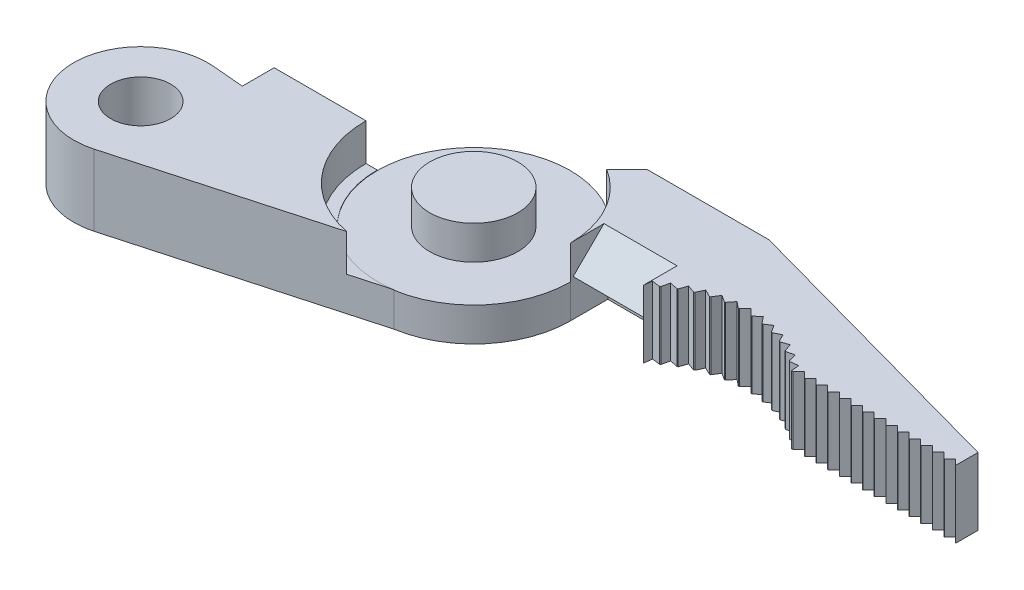
SolidWorks part; units mm, degrees
material "Plain Carbon Steel"
ref_plane "Front Plane" through (0, 0, 0) normal (0, 0, 1) x (1, 0, 0)
ref_plane "Top Plane" through (0, 0, 0) normal (0, 1, 0) x (1, 0, 0)
ref_plane "Right Plane" through (0, 0, 0) normal (1, 0, 0) x (0, 0, -1)
sketch "Sketch1" plane through (0, 0, 0) normal (0, 1, 0) x (1, 0, 0)
  circle A0 centre (0, 0) radius 6.5405
  circle A1 centre (0, 0) radius 2.9845
  dimension "D1" = 13.081
  dimension "D2" = 5.969
extrude "Boss-Extrude1" add sketch "Sketch1" along normal blind 4.826
sketch "Sketch2" plane through (0, 0, 0) normal (0, 1, 0) x (1, 0, 0)
  line L0 (-6.5405, 0) -> (-13.5255, 0)
  line L1 (-13.5255, 0) -> (-13.5255, -2.159)
  line L2 (-15.6763, -1.9708) -> (-13.5255, -2.159)
  line L3 (1.0584, -6.4543) -> (-14.8567, -10.8736)
  circle A1 centre (-16.0722, -6.4964) radius 2.032
  circle A2 centre (0, 0) radius 2.9845 construction
  arc A3 (-15.6763, -1.9708) -> (-14.8567, -10.8736) centre (-16.0722, -6.4964) ccw
  arc A4 (-6.5405, 0) -> (1.0584, -6.4543) centre (0, 0) ccw
  dimension "D1" = 4.064
  dimension "D6" = 17.3355
  dimension "D7" = 1.0584
  dimension "D3" = 4.5429
  dimension "D4" = 6.5405
  dimension "D2" = 6.985
  dimension "D5" = 85
extrude "Boss-Extrude2" add sketch "Sketch2" along normal up to surface (4.826 mm away) up to face at (0, 4.826, 6.5405)
hole_wizard "#43 (0.089) Diameter Hole1" positions "Sketch6" profile "Sketch7" hole size "#43" standard "ANSI Inch"
sketch "Sketch6" plane through (0, 0, 0) normal (0, 0, -1) x (-1, 0, 0)
  line L0 (13.5255, 4.826) -> (13.5255, 0) construction
  line L1 (6.5405, 0) -> (13.5255, 0) construction
  point P0 (10.033, 2.413)
  dimension "D1" = 3.4925
  dimension "D2" = 2.413
sketch "Sketch7" plane through (-10.033, 2.413, 0) normal (1, 0, 0) x (0, 1, 0)
  line L0 (0, 0) -> (0, 2.7112)
  line L1 (0, 2.7112) -> (1.1303, 2.032)
  line L2 (1.1303, 2.032) -> (1.1303, 0)
  line L5 (1.1303, 0) -> (0, 0)
  line L10 (0, 2.7112) -> (-1.1303, 2.032) construction
  line L11 (0, -6.35) -> (0, 107.95) construction
  dimension "Hole Dia." = 2.2606
  dimension "Hole Depth" = 2.032
  dimension "Drill Angle" = 118
sketch "Sketch8" plane through (0, 0, 0) normal (0, 1, 0) x (1, 0, 0)
  line L0 (13.081, 6.9215) -> (32.639, 1.524)
  line L1 (32.639, 1.524) -> (32.639, 0)
  line L2 (32.639, 0) -> (21.5265, 0)
  line L3 (13.081, 6.9215) -> (4.826, 6.9215)
  line L4 (4.826, 6.9215) -> (3.4568, 5.5523)
  line L5 (6.5405, 0) -> (11.4935, 0)
  arc A2 (1.0584, -6.4543) -> (-6.5405, 0) centre (0, 0) ccw construction
  arc A4 (21.5265, 0) -> (11.4935, 0) centre (16.51, -5.7358) ccw
  arc A5 (6.5405, 0) -> (3.4568, 5.5523) centre (0, 0) ccw
  dimension "D1" = 0.381
  dimension "D8" = 7.62
  dimension "D2" = 1.524
  dimension "D3" = 8.255
  dimension "D4" = 32.639
  dimension "D5" = 225
  dimension "D6" = 11.1125
  dimension "D7" = 4.953
  dimension "D9" = 4.826
extrude "Boss-Extrude3" add sketch "Sketch8" along normal up to surface (4.826 mm away) up to face at (-10.2367, 4.826, 2.2894)
sketch "Sketch9" plane through (0, 4.826, 0) normal (0, 1, 0) x (1, 0, 0)
  line L10 (-7.3025, 0) -> (-6.5405, 0)
  line L11 (-1.463, -7.1544) -> (1.0584, -6.4543)
  line L12 (-14.8567, -10.8736) -> (1.0584, -6.4543) construction
  line L32 (33.401, -0.762) -> (33.401, 2.1048)
  arc A4 (-7.3025, 0) -> (-1.463, -7.1544) centre (0, 0) ccw
  arc A5 (-6.5405, 0) -> (1.0584, -6.4543) centre (0, 0) ccw
  arc A6 (3.4568, 5.5523) -> (-6.5405, 0) centre (0, 0) ccw construction
  arc A7 (1.0584, -6.4543) -> (6.5405, 0) centre (0, 0) ccw construction
  line M26 (-6.5405, 0) -> (-13.5255, 0)
  line M30 (-14.8567, -10.8736) -> (1.0584, -6.4543)
  dimension "D1" = 7.3025
  dimension "D2" = 6.5405
  dimension "D3" = 2.6168
extrude "Cut-Extrude1" cut sketch "Sketch9" against normal blind 2.5082 contours A5 A4 M26 M30 region at (-6.9215, 4.826, 0.11)
sketch "Sketch10" plane through (0, 4.826, 0) normal (0, 1, 0) x (1, 0, 0)
  line L0 (32.639, 0) -> (32.258, 0.381)
  line L1 (32.258, 0.381) -> (31.877, 0)
  line L3 (21.5265, 0) -> (32.639, 0) construction
  line L4 (31.877, 0) -> (32.639, 0)
  dimension "D1" = 0.381
extrude "Cut-Extrude2" cut sketch "Sketch10" against normal through all
pattern_linear "LPattern1" count 14 spacing 0.7874 along (-1, 0, 0) of "Cut-Extrude2"
sketch "Sketch11" plane through (0, 4.826, 0) normal (0, 1, 0) x (1, 0, 0)
  line L0 (21.5265, 0) -> (21.4646, 0.5466)
  line L1 (21.4646, 0.5466) -> (20.9187, 0.4794)
  arc A0 (21.5265, 0) -> (11.4935, 0) centre (16.51, -5.7358) ccw construction
  arc A1 (21.5265, 0) -> (20.9187, 0.4794) centre (16.51, -5.7358) ccw
  dimension "D1" = 8.001
extrude "Cut-Extrude3" cut sketch "Sketch11" against normal through all
pattern_circular "CirPattern1" count 13 over 76.5 about axis through (16.51, 4.826, 5.7358) along (0, -1, 0) of "Cut-Extrude3" reverse direction yes
sketch "Sketch13" plane through (0, 4.826, 0) normal (0, 1, 0) x (1, 0, 0)
  line L0 (11.4935, 0) -> (11.4935, 2.54)
  line L1 (11.4935, 2.54) -> (6.5405, 2.54)
  line L2 (6.5405, 2.54) -> (6.5405, 0)
  line L3 (6.5405, 0) -> (11.4935, 0)
  dimension "D1" = 2.54
extrude "Cut-Extrude5" cut sketch "Sketch13" against normal blind 2.5082
sketch "Sketch14" plane through (6.5405, 0, 0) normal (1, 0, 0) x (0, 0, -1)
  line L0 (0, 2.3178) -> (2.54, 4.826)
  line L1 (2.54, 4.826) -> (2.54, 2.3177)
  line L2 (2.54, 2.3177) -> (2.54, 4.826) construction
  line L3 (2.54, 2.3177) -> (0, 2.3178) construction
  line L4 (2.54, 2.3177) -> (0, 2.3178)
extrude "Boss-Extrude4" add sketch "Sketch14" along normal up to next
sketch "Sketch15" plane through (0, 0, 0) normal (0, -1, 0) x (1, 0, 0)
  line L0 (6.5405, 0) -> (6.5405, -2.54)
  line L1 (6.5405, 0) -> (11.4935, 0) construction
  line L2 (6.5405, -2.54) -> (11.4935, -2.54)
  line L3 (11.4935, -2.54) -> (11.4935, 0)
  line L4 (11.4935, 0) -> (6.5405, 0)
  arc A0 (6.5405, 0) -> (1.0584, 6.4543) centre (0, 0) ccw construction
  dimension "D1" = 2.54
extrude "Cut-Extrude6" cut sketch "Sketch15" against normal blind 2.5082
sketch "Sketch16" plane through (0, 4.826, 0) normal (0, 1, 0) x (1, 0, 0)
  circle A0 centre (0, 0) radius 6.5405
extrude "Cut-Extrude7" cut sketch "Sketch16" against normal blind 2.54
sketch "Sketch18" plane through (0, 0, 0) normal (0, 1, 0) x (1, 0, 0)
  circle A0 centre (0, 0) radius 2.9845
  dimension "D1" = 5.969
extrude "Boss-Extrude5" add sketch "Sketch18" along normal blind 4.572
sketch "Sketch19" plane through (0, 4.826, 0) normal (0, 1, 0) x (1, 0, 0)
  line L76 (6.5405, 0) -> (6.5405, 2.54)
  line L77 (6.5405, 2.54) -> (11.4935, 2.54)
  line L78 (11.4935, 2.54) -> (11.4935, 0)
  line L79 (11.4935, 0) -> (11.4958, 0.002)
  line L80 (11.4958, 0.002) -> (11.5579, 0.5485)
  line L81 (11.5579, 0.5485) -> (12.1038, 0.4811)
  line L82 (12.1639, 0.5233) -> (12.2863, 1.0595)
  line L83 (12.2863, 1.0595) -> (12.8213, 0.9319)
  line L84 (12.8857, 0.9671) -> (13.0669, 1.4865)
  line L85 (13.0669, 1.4865) -> (13.5845, 1.3003)
  line L86 (13.6524, 1.3281) -> (13.8901, 1.8241)
  line L87 (13.8901, 1.8241) -> (14.3838, 1.5816)
  line L88 (14.4544, 1.6017) -> (14.7457, 2.0683)
  line L89 (14.7457, 2.0683) -> (15.2095, 1.7724)
  line L90 (15.2818, 1.7846) -> (15.6232, 2.2159)
  line L91 (15.6232, 2.2159) -> (16.0512, 1.8704)
  line L92 (16.1244, 1.8745) -> (16.5116, 2.2652)
  line L93 (16.5116, 2.2652) -> (16.8986, 1.8743)
  line L94 (16.9718, 1.8702) -> (17.4, 2.2156)
  line L95 (17.4, 2.2156) -> (17.7411, 1.7841)
  line L96 (17.8135, 1.7719) -> (18.2773, 2.0676)
  line L97 (18.2773, 2.0676) -> (18.5685, 1.6009)
  line L98 (18.6391, 1.5807) -> (19.1329, 1.8231)
  line L99 (19.1329, 1.8231) -> (19.3704, 1.327)
  line L100 (19.4383, 1.2991) -> (19.9559, 1.4851)
  line L101 (19.9559, 1.4851) -> (20.1369, 0.9657)
  line L102 (20.2013, 0.9305) -> (20.7364, 1.0579)
  line L103 (20.7364, 1.0579) -> (20.8586, 0.5215)
  line L104 (20.9187, 0.4794) -> (21.4646, 0.5466)
  line L105 (21.4646, 0.5466) -> (21.5265, 0)
  line L106 (21.5265, 0) -> (21.6408, 0)
  line L107 (21.6408, 0) -> (22.0218, 0.381)
  line L108 (22.0218, 0.381) -> (22.4028, 0)
  line L109 (22.4028, 0) -> (22.4282, 0)
  line L110 (22.4282, 0) -> (22.8092, 0.381)
  line L111 (22.8092, 0.381) -> (23.1902, 0)
  line L112 (23.1902, 0) -> (23.2156, 0)
  line L113 (23.2156, 0) -> (23.5966, 0.381)
  line L114 (23.5966, 0.381) -> (23.9776, 0)
  line L115 (23.9776, 0) -> (24.003, 0)
  line L116 (24.003, 0) -> (24.384, 0.381)
  line L117 (24.384, 0.381) -> (24.765, 0)
  line L118 (24.765, 0) -> (24.7904, 0)
  line L119 (24.7904, 0) -> (25.1714, 0.381)
  line L120 (25.1714, 0.381) -> (25.5524, 0)
  line L121 (25.5524, 0) -> (25.5778, 0)
  line L122 (25.5778, 0) -> (25.9588, 0.381)
  line L123 (25.9588, 0.381) -> (26.3398, 0)
  line L124 (26.3398, 0) -> (26.3652, 0)
  line L125 (26.3652, 0) -> (26.7462, 0.381)
  line L126 (26.7462, 0.381) -> (27.1272, 0)
  line L127 (27.1272, 0) -> (27.1526, 0)
  line L128 (27.1526, 0) -> (27.5336, 0.381)
  line L129 (27.5336, 0.381) -> (27.9146, 0)
  line L130 (27.9146, 0) -> (27.94, 0)
  line L131 (27.94, 0) -> (28.321, 0.381)
  line L132 (28.321, 0.381) -> (28.702, 0)
  line L133 (28.702, 0) -> (28.7274, 0)
  line L134 (28.7274, 0) -> (29.1084, 0.381)
  line L135 (29.1084, 0.381) -> (29.4894, 0)
  line L136 (29.4894, 0) -> (29.5148, 0)
  line L137 (29.5148, 0) -> (29.8958, 0.381)
  line L138 (29.8958, 0.381) -> (30.2768, 0)
  line L139 (30.2768, 0) -> (30.3022, 0)
  line L140 (30.3022, 0) -> (30.6832, 0.381)
  line L141 (30.6832, 0.381) -> (31.0642, 0)
  line L142 (31.0642, 0) -> (31.0896, 0)
  line L143 (31.0896, 0) -> (31.4706, 0.381)
  line L144 (31.4706, 0.381) -> (31.8516, 0)
  line L145 (31.8516, 0) -> (31.877, 0)
  line L146 (31.877, 0) -> (32.258, 0.381)
  line L147 (32.258, 0.381) -> (32.639, 0)
  line L148 (32.639, 0) -> (32.639, 1.524)
  line L149 (32.639, 1.524) -> (13.081, 6.9215)
  line L150 (13.081, 6.9215) -> (4.826, 6.9215)
  line L151 (4.826, 6.9215) -> (3.4568, 5.5523)
  line L152 (6.5405, 0) -> (6.5405, 2.54)
  line L153 (6.5405, 2.54) -> (11.4935, 2.54)
  line L154 (11.4935, 2.54) -> (11.4935, 0)
  line L155 (11.4935, 0) -> (11.4958, 0.002)
  line L156 (11.4958, 0.002) -> (11.5579, 0.5485)
  line L157 (11.5579, 0.5485) -> (12.1038, 0.4811)
  line L158 (12.1639, 0.5233) -> (12.2863, 1.0595)
  line L159 (12.2863, 1.0595) -> (12.8213, 0.9319)
  line L160 (12.8857, 0.9671) -> (13.0669, 1.4865)
  line L161 (13.0669, 1.4865) -> (13.5845, 1.3003)
  line L162 (13.6524, 1.3281) -> (13.8901, 1.8241)
  line L163 (13.8901, 1.8241) -> (14.3838, 1.5816)
  line L164 (14.4544, 1.6017) -> (14.7457, 2.0683)
  line L165 (14.7457, 2.0683) -> (15.2095, 1.7724)
  line L166 (15.2818, 1.7846) -> (15.6232, 2.2159)
  line L167 (15.6232, 2.2159) -> (16.0512, 1.8704)
  line L168 (16.1244, 1.8745) -> (16.5116, 2.2652)
  line L169 (16.5116, 2.2652) -> (16.8986, 1.8743)
  line L170 (16.9718, 1.8702) -> (17.4, 2.2156)
  line L171 (17.4, 2.2156) -> (17.7411, 1.7841)
  line L172 (17.8135, 1.7719) -> (18.2773, 2.0676)
  line L173 (18.2773, 2.0676) -> (18.5685, 1.6009)
  line L174 (18.6391, 1.5807) -> (19.1329, 1.8231)
  line L175 (19.1329, 1.8231) -> (19.3704, 1.327)
  line L176 (19.4383, 1.2991) -> (19.9559, 1.4851)
  line L177 (19.9559, 1.4851) -> (20.1369, 0.9657)
  line L178 (20.2013, 0.9305) -> (20.7364, 1.0579)
  line L179 (20.7364, 1.0579) -> (20.8586, 0.5215)
  line L180 (20.9187, 0.4794) -> (21.4646, 0.5466)
  line L181 (21.4646, 0.5466) -> (21.5265, 0)
  line L182 (21.5265, 0) -> (21.6408, 0)
  line L183 (21.6408, 0) -> (22.0218, 0.381)
  line L184 (22.0218, 0.381) -> (22.4028, 0)
  line L185 (22.4028, 0) -> (22.4282, 0)
  line L186 (22.4282, 0) -> (22.8092, 0.381)
  line L187 (22.8092, 0.381) -> (23.1902, 0)
  line L188 (23.1902, 0) -> (23.2156, 0)
  line L189 (23.2156, 0) -> (23.5966, 0.381)
  line L190 (23.5966, 0.381) -> (23.9776, 0)
  line L191 (23.9776, 0) -> (24.003, 0)
  line L192 (24.003, 0) -> (24.384, 0.381)
  line L193 (24.384, 0.381) -> (24.765, 0)
  line L194 (24.765, 0) -> (24.7904, 0)
  line L195 (24.7904, 0) -> (25.1714, 0.381)
  line L196 (25.1714, 0.381) -> (25.5524, 0)
  line L197 (25.5524, 0) -> (25.5778, 0)
  line L198 (25.5778, 0) -> (25.9588, 0.381)
  line L199 (25.9588, 0.381) -> (26.3398, 0)
  line L200 (26.3398, 0) -> (26.3652, 0)
  line L201 (26.3652, 0) -> (26.7462, 0.381)
  line L202 (26.7462, 0.381) -> (27.1272, 0)
  line L203 (27.1272, 0) -> (27.1526, 0)
  line L204 (27.1526, 0) -> (27.5336, 0.381)
  line L205 (27.5336, 0.381) -> (27.9146, 0)
  line L206 (27.9146, 0) -> (27.94, 0)
  line L207 (27.94, 0) -> (28.321, 0.381)
  line L208 (28.321, 0.381) -> (28.702, 0)
  line L209 (28.702, 0) -> (28.7274, 0)
  line L210 (28.7274, 0) -> (29.1084, 0.381)
  line L211 (29.1084, 0.381) -> (29.4894, 0)
  line L212 (29.4894, 0) -> (29.5148, 0)
  line L213 (29.5148, 0) -> (29.8958, 0.381)
  line L214 (29.8958, 0.381) -> (30.2768, 0)
  line L215 (30.2768, 0) -> (30.3022, 0)
  line L216 (30.3022, 0) -> (30.6832, 0.381)
  line L217 (30.6832, 0.381) -> (31.0642, 0)
  line L218 (31.0642, 0) -> (31.0896, 0)
  line L219 (31.0896, 0) -> (31.4706, 0.381)
  line L220 (31.4706, 0.381) -> (31.8516, 0)
  line L221 (31.8516, 0) -> (31.877, 0)
  line L222 (31.877, 0) -> (32.258, 0.381)
  line L223 (32.258, 0.381) -> (32.639, 0)
  line L224 (32.639, 0) -> (32.639, 1.524)
  line L225 (32.639, 1.524) -> (13.081, 6.9215)
  line L226 (13.081, 6.9215) -> (4.826, 6.9215)
  line L227 (4.826, 6.9215) -> (3.4568, 5.5523)
  arc A13 (6.5405, 0) -> (3.4568, 5.5523) centre (0, 0) ccw
  arc A14 (12.1639, 0.5233) -> (12.1038, 0.4811) centre (16.51, -5.7358) ccw
  arc A15 (12.8857, 0.9671) -> (12.8213, 0.9319) centre (16.51, -5.7358) ccw
  arc A16 (13.6524, 1.3281) -> (13.5845, 1.3003) centre (16.51, -5.7358) ccw
  arc A17 (14.4544, 1.6017) -> (14.3838, 1.5816) centre (16.51, -5.7358) ccw
  arc A18 (15.2818, 1.7846) -> (15.2095, 1.7724) centre (16.51, -5.7358) ccw
  arc A19 (16.1244, 1.8745) -> (16.0512, 1.8704) centre (16.51, -5.7358) ccw
  arc A20 (16.9718, 1.8702) -> (16.8986, 1.8743) centre (16.51, -5.7358) ccw
  arc A21 (17.8135, 1.7719) -> (17.7411, 1.7841) centre (16.51, -5.7358) ccw
  arc A22 (18.6391, 1.5807) -> (18.5685, 1.6009) centre (16.51, -5.7358) ccw
  arc A23 (19.4383, 1.2991) -> (19.3704, 1.327) centre (16.51, -5.7358) ccw
  arc A24 (20.2013, 0.9305) -> (20.1369, 0.9657) centre (16.51, -5.7358) ccw
  arc A25 (20.9187, 0.4794) -> (20.8586, 0.5215) centre (16.51, -5.7358) ccw
  arc A26 (6.5405, 0) -> (3.4568, 5.5523) centre (0, 0) ccw
  arc A27 (12.1639, 0.5233) -> (12.1038, 0.4811) centre (16.51, -5.7358) ccw
  arc A28 (12.8857, 0.9671) -> (12.8213, 0.9319) centre (16.51, -5.7358) ccw
  arc A29 (13.6524, 1.3281) -> (13.5845, 1.3003) centre (16.51, -5.7358) ccw
  arc A30 (14.4544, 1.6017) -> (14.3838, 1.5816) centre (16.51, -5.7358) ccw
  arc A31 (15.2818, 1.7846) -> (15.2095, 1.7724) centre (16.51, -5.7358) ccw
  arc A32 (16.1244, 1.8745) -> (16.0512, 1.8704) centre (16.51, -5.7358) ccw
  arc A33 (16.9718, 1.8702) -> (16.8986, 1.8743) centre (16.51, -5.7358) ccw
  arc A34 (17.8135, 1.7719) -> (17.7411, 1.7841) centre (16.51, -5.7358) ccw
  arc A35 (18.6391, 1.5807) -> (18.5685, 1.6009) centre (16.51, -5.7358) ccw
  arc A36 (19.4383, 1.2991) -> (19.3704, 1.327) centre (16.51, -5.7358) ccw
  arc A37 (20.2013, 0.9305) -> (20.1369, 0.9657) centre (16.51, -5.7358) ccw
  arc A38 (20.9187, 0.4794) -> (20.8586, 0.5215) centre (16.51, -5.7358) ccw
  dimension "D1" = 0
extrude "Cut-Extrude8" cut sketch "Sketch19" against normal blind 0.254
sketch "Sketch20" plane through (11.4935, 0, 0) normal (1, 0, 0) x (0, 0, -1)
  line L0 (2.54, 4.826) -> (2.2828, 4.572)
  line L1 (2.2828, 4.572) -> (2.54, 4.572)
  line L2 (2.54, 4.572) -> (2.54, 4.826)
extrude "Cut-Extrude9" cut sketch "Sketch20" against normal up to next
